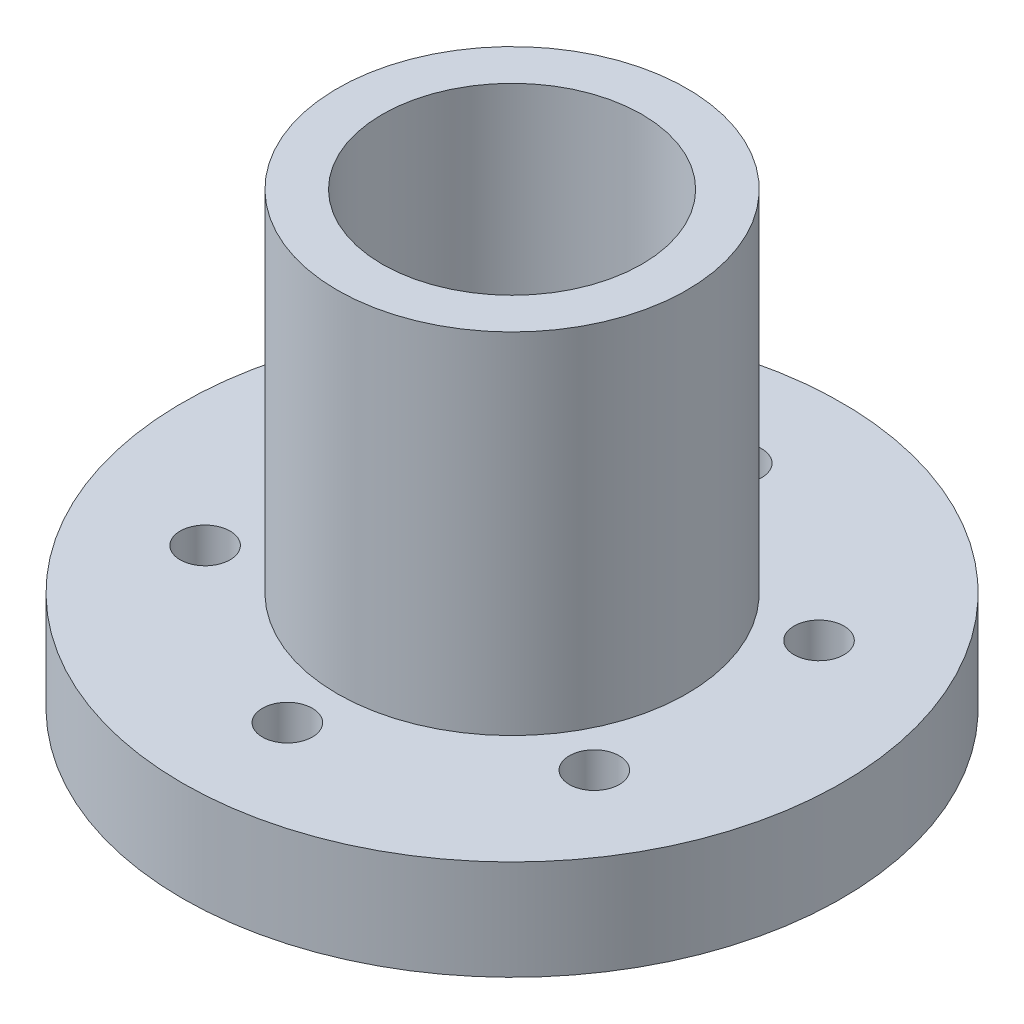
SolidWorks part; units mm, degrees
ref_plane "Front Plane" through (0, 0, 0) normal (0, 0, 1) x (1, 0, 0)
ref_plane "Top Plane" through (0, 0, 0) normal (0, 1, 0) x (1, 0, 0)
ref_plane "Right Plane" through (0, 0, 0) normal (1, 0, 0) x (0, 0, -1)
sketch "Sketch1" plane through (0, 0, 0) normal (0, 1, 0) x (1, 0, 0)
  circle A0 centre (0, 0) radius 33
  circle A1 centre (0, 0) radius 22.5 construction
  circle A2 centre (0, 0) radius 5
  circle A3 centre (0, 22.5) radius 2.5
  circle A4 centre (19.4856, 11.25) radius 2.5
  circle A5 centre (19.4856, -11.25) radius 2.5
  circle A6 centre (0, -22.5) radius 2.5
  circle A7 centre (-19.4856, -11.25) radius 2.5
  circle A8 centre (-19.4856, 11.25) radius 2.5
  point P19 (0, 0)
  dimension "D1" = 66
  dimension "D2" = 10
  dimension "D3" = 45
  dimension "D4" = 5
  dimension "D5" = 6
extrude "Boss-Extrude1" add sketch "Sketch1" along normal blind 10
sketch "Sketch2" plane through (0, 0, 0) normal (0, -1, 0) x (1, 0, 0)
  circle A0 centre (0, 0) radius 16
  dimension "D1" = 32
extrude "Cut-Extrude1" cut sketch "Sketch2" against normal blind 5
sketch "Sketch5" plane through (0, 10, 0) normal (0, 1, 0) x (1, 0, 0)
  circle A0 centre (0, 0) radius 13
  dimension "D1" = 26
extrude "Cut-Extrude2" cut sketch "Sketch5" against normal up to surface (5 mm away) up to face at (0, 5, -5)
sketch "Sketch6" plane through (0, 10, 0) normal (0, 1, 0) x (1, 0, 0)
  circle A0 centre (0, 0) radius 13
  circle A1 centre (0, 0) radius 17.5
  circle A2 centre (0, 0) radius 13 construction
  dimension "D1" = 35
extrude "Boss-Extrude2" add sketch "Sketch6" along normal blind 35
